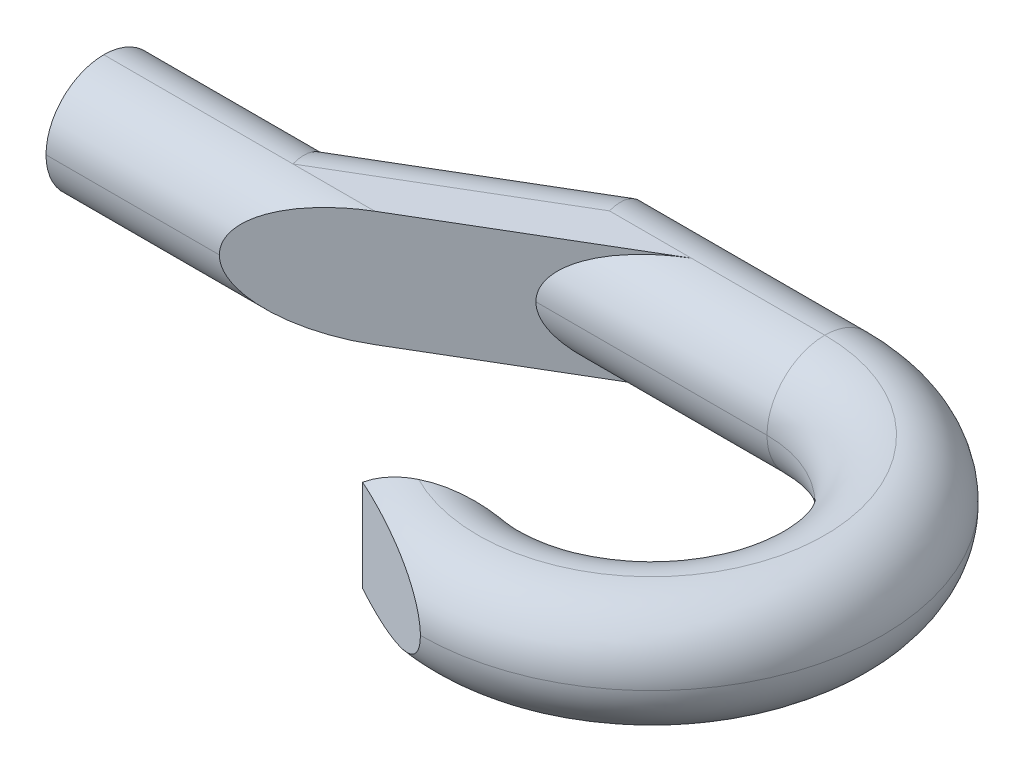
SolidWorks part; units mm, degrees
ref_plane "Спереди" through (0, 0, 0) normal (0, 0, 1) x (1, 0, 0)
ref_plane "Сверху" through (0, 0, 0) normal (0, 1, 0) x (1, 0, 0)
ref_plane "Справа" through (0, 0, 0) normal (1, 0, 0) x (0, 0, -1)
sketch "Эскиз2" plane through (0, 0, 0) normal (0, 1, 0) x (1, 0, 0)
  line L6 (10, -25) -> (20, -20)
  line L7 (10, -25) -> (20, -30)
  line L9 (20, 10) -> (0, 10)
  line L11 (20, 0) -> (0, 0)
  line L13 (0, 10) -> (-17.2152, -0.1802)
  line L14 (0, 0) -> (-17.2152, -10.1802)
  line L17 (-17.2152, -0.1802) -> (-32.2152, -0.1802)
  line L19 (-17.2152, -10.1802) -> (-32.2152, -10.1802)
  line L20 (-32.2152, -0.1802) -> (-32.2152, -10.1802)
  arc A0 (20, 0) -> (20, -20) centre (20, -10) cw
  arc A1 (20, 10) -> (20, -30) centre (20, -10) cw
  point P9 (0, 0)
extrude "Бобышка-Вытянуть1" add sketch "Эскиз2" along normal blind 10
fillet "Скругление5" radius 5 6 edges at (30, 10, 10) (30, 0, 10) (10, 10, 0) (10, 0, 0) (-24.7152, 10, 10.1802) (-24.7152, 0, 10.1802)
fillet "Скругление6" radius 5 8 edges at (40, 10, 10) (40, 0, 10) (10, 10, -10) (10, 0, -10) (-8.6076, 10, -4.9099) (-8.6076, 0, -4.9099) (-24.7152, 10, 0.1802) (-24.7152, 0, 0.1802)
sketch "Эскиз22" plane through (-32.2152, 0, 0) normal (-1, 0, 0) x (0, 0, 1)
  circle A0 centre (5.1802, 5) radius 2.8
  dimension "D1" = 5.6
extrude "Вырез-Вытянуть1" cut sketch "Эскиз22" against normal blind 3.4 contours A0
